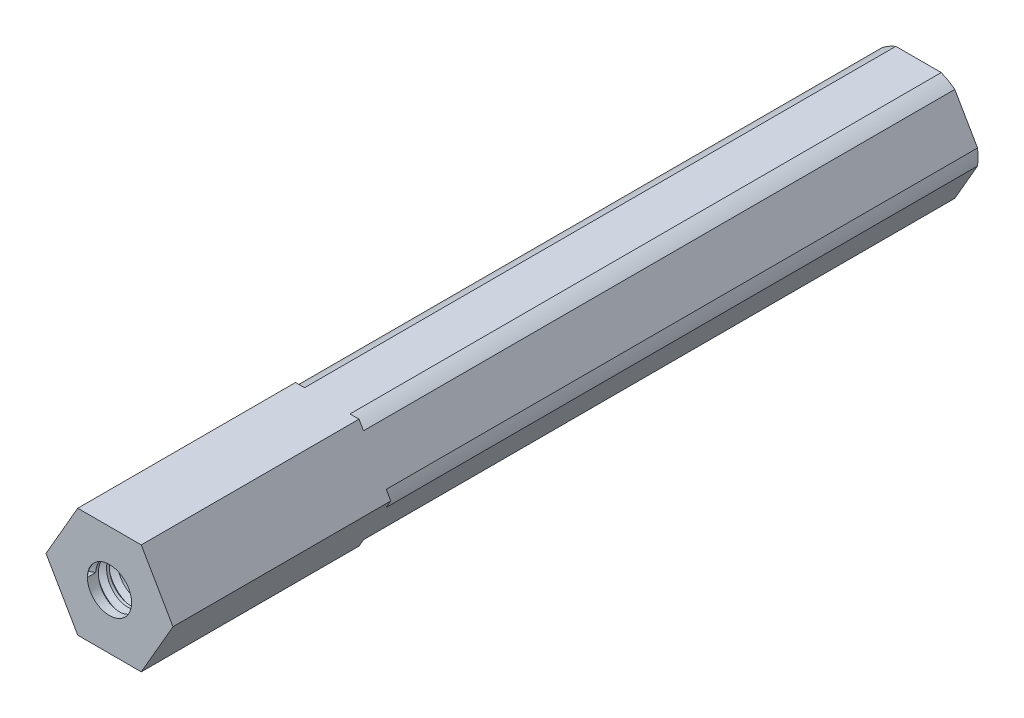
SolidWorks part; units mm, degrees
material "7075-T6 (SN)"
ref_plane "Alzado" through (0, 0, 0) normal (0, 0, 1) x (1, 0, 0)
ref_plane "Planta" through (0, 0, 0) normal (0, 1, 0) x (1, 0, 0)
ref_plane "Vista lateral" through (0, 0, 0) normal (1, 0, 0) x (0, 0, -1)
sketch "Croquis2" plane through (0, 0, 0) normal (0, 0, 1) x (1, 0, 0)
  line L1 (3.6662, -6.35) -> (7.3323, 0)
  line L2 (7.3323, 0) -> (3.6662, 6.35)
  line L3 (3.6662, 6.35) -> (-3.6662, 6.35)
  line L4 (-3.6662, 6.35) -> (-7.3323, 0)
  line L5 (-7.3323, 0) -> (-3.6662, -6.35)
  line L6 (-3.6662, -6.35) -> (3.6662, -6.35)
  circle A0 centre (0, 0) radius 6.35 construction
  dimension "D1" = 12.7
extrude "Extrusión Hex Profile" add sketch "Croquis2" along normal mid plane 93.4212
sketch "Croquis3" plane through (0, 0, 0) normal (0, 0, 1) x (1, 0, 0)
  circle A0 centre (0, 0) radius 2.5527
  dimension "D1" = 5.1054
extrude "Tap Hole 1" cut sketch "Croquis3" against normal blind 19.05 from surface starting at face at (0, 0, 46.7106)
extrude "Tap Hole 2" cut sketch "Croquis3<3>" along normal blind 19.05 from surface starting at face at (0, 0, -46.7106)
sketch "Croquis3<3>" plane through (0, 0, 0) normal (0, 0, 1) x (1, 0, 0) same geometry as "Croquis3"
sketch "Croquis7" plane through (0, 0, 0) normal (0, 0, 1) x (1, 0, 0)
  circle A0 centre (0, 0) radius 6.8707
  dimension "D1" = 13.7414
extrude "ThunderHex" cut sketch "Croquis7" along normal offset from surface (68.2752 mm away) 25.146 from surface flip side to cut up to face at (2.5527, 0, 46.7106) starting at face at (2.5527, 0, -46.7106)
sketch "Croquis8" plane through (0, 0, 0) normal (0, 1, 0) x (1, 0, 0)
  line L0 (0, -46.7106) -> (-5.5562, -46.7106) construction
  line L1 (3.6662, -46.7106) -> (-3.6662, -46.7106) construction
  line L3 (0, -46.7106) -> (0, 0) construction
  line L4 (-5.5562, -46.7106) -> (-6.35, -45.9169)
  line L5 (-6.35, -45.9169) -> (-6.35, -45.1231)
  line L6 (-6.35, -45.1231) -> (-5.9055, -45.1231)
  line L7 (-5.9055, -45.1231) -> (-5.9055, -43.5356)
  line L8 (-5.9055, -43.5356) -> (-12.7, -43.5356)
  line L9 (-12.7, -43.5356) -> (-12.7, -46.7106)
  line L10 (-12.7, -46.7106) -> (-5.5562, -46.7106)
  line L11 (-3.6662, -46.7106) -> (-7.3323, -46.7106) construction
  dimension "D1" = 11.811
  dimension "D2" = 12.7
  dimension "D3" = 45
  dimension "D4" = 0.7937
  dimension "D6" = 0.7937
  dimension "D7" = 3.175
  dimension "D8" = 25.4
revolve "Retaining Ring 1" [suppressed] cut sketch "Croquis8" angle 360 about L3
sketch "Croquis9" plane through (0, 0, 0) normal (0, -1, 0) x (1, 0, 0)
  line L0 (0, -46.7106) -> (-5.5562, -46.7106) construction
  line L3 (0, -46.7106) -> (0, 0) construction
  line L4 (-5.5562, -46.7106) -> (-6.35, -45.9169)
  line L5 (-6.35, -45.9169) -> (-6.35, -45.1231)
  line L6 (-6.35, -45.1231) -> (-5.9055, -45.1231)
  line L7 (-5.9055, -45.1231) -> (-5.9055, -43.5356)
  line L8 (-5.9055, -43.5356) -> (-12.7, -43.5356)
  line L9 (-12.7, -43.5356) -> (-12.7, -46.7106)
  line L10 (-12.7, -46.7106) -> (-5.5562, -46.7106)
  line L12 (-2.6237, -46.7106) -> (2.6237, -46.7106) construction
  line L13 (-6.8111, -46.7106) -> (-4.1874, -46.7106) construction
  dimension "D1" = 11.811
  dimension "D2" = 12.7
  dimension "D3" = 45
  dimension "D4" = 0.7937
  dimension "D6" = 0.7937
  dimension "D7" = 3.175
  dimension "D8" = 25.4
revolve "Retaining Ring 2" [suppressed] cut sketch "Croquis9" angle 360 about L3
sketch "Croquis10" plane through (0, 0, 0) normal (0, 1, 0) x (1, 0, 0)
  line L0 (0, -46.7106) -> (0, 0) construction
  line L1 (3.6662, -46.7106) -> (-3.6662, -46.7106) construction
  line L2 (0, -46.7106) -> (-5.5562, -46.7106) construction
  line L3 (-3.6662, -46.7106) -> (-7.3323, -46.7106) construction
  line L4 (-5.5562, -46.7106) -> (-6.35, -45.9169)
  line L5 (-6.35, -45.9169) -> (-6.35, -38.7604)
  line L6 (-6.35, -38.7604) -> (-9.525, -38.7604)
  line L7 (-9.525, -38.7604) -> (-9.525, -46.7106)
  line L8 (-9.525, -46.7106) -> (-5.5562, -46.7106)
  dimension "D2" = 12.7
  dimension "D1" = 45
  dimension "D3" = 0.7937
  dimension "D4" = 7.9502
  dimension "D5" = 19.05
revolve "Round End 1" [suppressed] cut sketch "Croquis10" angle 360 about L0
sketch "Croquis12" plane through (0, 0, 0) normal (0, -1, 0) x (1, 0, 0)
  line L0 (0, -46.7106) -> (0, 0) construction
  line L2 (0, -46.7106) -> (-5.5562, -46.7106) construction
  line L4 (-5.5562, -46.7106) -> (-6.35, -45.9169)
  line L5 (-6.35, -45.9169) -> (-6.35, -38.7604)
  line L6 (-6.35, -38.7604) -> (-9.525, -38.7604)
  line L7 (-9.525, -38.7604) -> (-9.525, -46.7106)
  line L8 (-9.525, -46.7106) -> (-5.5562, -46.7106)
  line L9 (-2.6237, -46.7106) -> (2.6237, -46.7106) construction
  dimension "D1" = 45
  dimension "D3" = 0.7937
  dimension "D4" = 7.9502
  dimension "D2" = 12.7
  dimension "D5" = 19.05
revolve "Round End 2" [suppressed] cut sketch "Croquis12" angle 360 about L0
thread "Rosca1" pitch 1.27 method cut profile "Perfil de rosca1" start angle 0, offset 0, length 0, pitch 1.27, diameter 5.1054
ref_plane "Plano1" through (-2.5527, 0, 46.7106) normal (0, -1, 0) x (-1, 0, 0)
sketch "Perfil de rosca1" plane through (-2.5527, 0, 46.7106) normal (0, -1, 0) x (-1, 0, 0)
  line L0 (0, 0) -> (0, 1.27) construction
  line L1 (0, 0) -> (0.6874, 0.3969)
  line L2 (0.6874, 0.3969) -> (0.6874, 0.5556)
  line L3 (0.6874, 0.5556) -> (0, 0.9525)
  line L4 (0.6874, 0.4762) -> (0, 0.4762) construction
  line L11 (0, 0) -> (0, 0.9525)
  point P2 (0, 0)
  dimension "Pitch" = 1.27
  dimension "Profile_Angle" = 60
  dimension "Profile_Land" = 0.1588
  dimension "Profile_Height" = 0.6874
thread "Rosca2" pitch 1.27 method cut profile "Perfil de rosca2" start angle 0, offset 0, length 0, pitch 1.27, diameter 5.1054
ref_plane "Plano2" through (2.5527, 0, -46.7106) normal (0, -1, 0) x (1, 0, 0)
sketch "Perfil de rosca2" plane through (2.5527, 0, -46.7106) normal (0, -1, 0) x (1, 0, 0)
  line L0 (0, 0) -> (0, 1.27) construction
  line L1 (0, 0) -> (0.6874, 0.3969)
  line L2 (0.6874, 0.3969) -> (0.6874, 0.5556)
  line L3 (0.6874, 0.5556) -> (0, 0.9525)
  line L4 (0.6874, 0.4762) -> (0, 0.4762) construction
  line L11 (0, 0) -> (0, 0.9525)
  point P2 (0, 0)
  dimension "Pitch" = 1.27
  dimension "Profile_Angle" = 60
  dimension "Profile_Land" = 0.1588
  dimension "Profile_Height" = 0.6874
equation "\"HexOD\"= 0.5pulgadas"
equation "\"Largo\"= 3.678pulgadas"
equation "\"D1@Croquis2\"=\"HexOD\""
equation "\"D1@Extrusión Hex Profile\" = \"Largo\""
equation "\"TapHole\"= IIF ( \"HexOD\" = 0.5pulgadas , 0.2010pulgadas , 0.190pulgadas )"
equation "\"D1@Croquis3\"=\"TapHole\""
equation "\"ProTapHole\"= 0.75pulgadas"
equation "\"D1@Tap Hole 1\" = \"ProTapHole\""
equation "\"D1@Tap Hole 2\" = \"ProTapHole\""
equation "\"ThunderHex\"= IIF ( \"HexOD\" = 0.5pulgadas , 0.541pulgadas , 0.4035pulgadas )"
equation "\"D1@Croquis7\"=\"ThunderHex\""
equation "\"D2@Croquis8\"=\"HexOD\""
equation "\"D1@Croquis8\"=if(\"HexOD\"=0.5pulgadas, 0.465pulgadas, 0.35pulgadas )"
equation "\"D2@Croquis9\"=\"HexOD\""
equation "\"D1@Croquis9\"=if(\"HexOD\"=0.5pulgadas, 0.465pulgadas, 0.35pulgadas )"
equation "\"D8@Croquis8\"=\"HexOD\"*2"
equation "\"D8@Croquis9\"=\"HexOD\"*2"
equation "\"D5@Croquis10\"=\"HexOD\"*1.5"
equation "\"D5@Croquis12\"=\"HexOD\"*1.5"
equation "\"D4@Croquis10\"=if( \"D2@Croquis10\"=<0.375, 0.28, 0.313)"
equation "\"D4@Croquis12\"=if( \"D2@Croquis10\"=<0.375, 0.28, 0.313)"
